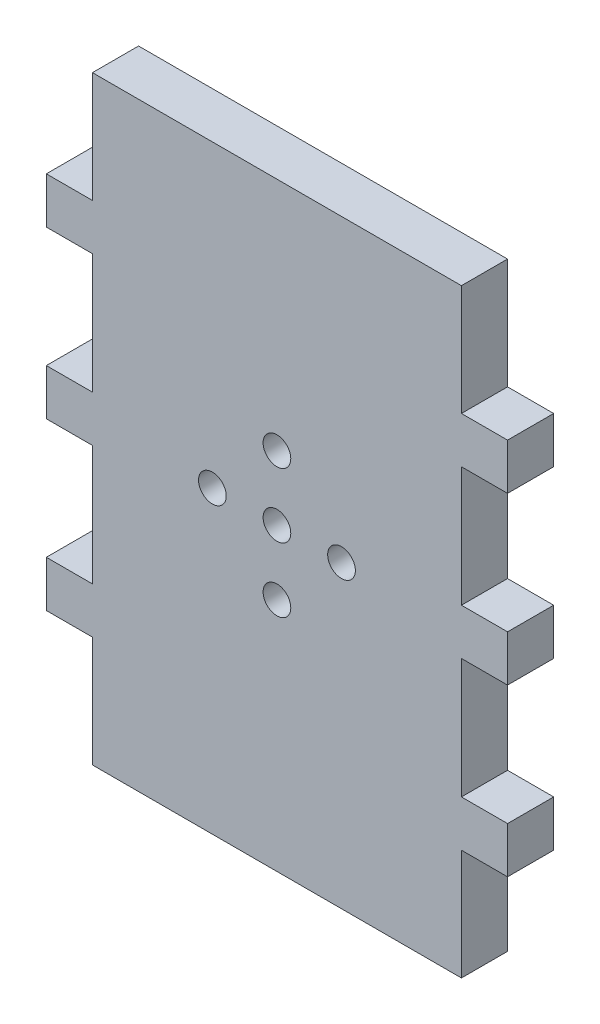
SolidWorks part; units mm, degrees
ref_plane "前视基准面" through (0, 0, 0) normal (0, 0, 1) x (1, 0, 0)
ref_plane "上视基准面" through (0, 0, 0) normal (0, 1, 0) x (1, 0, 0)
ref_plane "右视基准面" through (0, 0, 0) normal (1, 0, 0) x (0, 0, -1)
other "Configuration Table"
sketch "草图3" plane through (0, 0, 0) normal (0, 0, 1) x (1, 0, 0)
  line L0 (0, 0) -> (0, -12)
  line L1 (0, 0) -> (40, 0)
  line L3 (0, -65) -> (40, -65)
  line L4 (40, 0) -> (40, -12)
  line L5 (-5, -12) -> (-5, -17)
  line L6 (20, 0) -> (20, -65) construction
  line L7 (40, -12) -> (45, -12)
  line L8 (45, -12) -> (45, -17)
  line L9 (45, -17) -> (40, -17)
  line L10 (40, -17) -> (40, -30)
  line L11 (40, -30) -> (45, -30)
  line L12 (45, -30) -> (45, -35)
  line L13 (45, -35) -> (40, -35)
  line L14 (40, -65) -> (40, -53)
  line L15 (40, -53) -> (45, -53)
  line L16 (45, -53) -> (45, -48)
  line L17 (45, -48) -> (40, -48)
  line L18 (-5, -48) -> (0, -48)
  line L19 (-5, -53) -> (-5, -48)
  line L20 (0, -53) -> (-5, -53)
  line L21 (-5, -35) -> (0, -35)
  line L22 (-5, -30) -> (-5, -35)
  line L23 (0, -30) -> (-5, -30)
  line L24 (-5, -17) -> (0, -17)
  line L26 (0, -12) -> (-5, -12)
  line L27 (0, -17) -> (0, -30)
  line L28 (0, -35) -> (0, -48)
  line L29 (0, -53) -> (0, -65)
  line L31 (40, -35) -> (40, -48)
  circle A0 centre (20, -32.5) radius 1.5
  circle A2 centre (27, -32.5) radius 1.5
  circle A3 centre (20, -25.5) radius 1.5
  circle A4 centre (13, -32.5) radius 1.5
  circle A5 centre (20, -39.5) radius 1.5
  dimension "D6" = 3
  dimension "D12" = 3
  dimension "D13" = 3
  dimension "D14" = 3
  dimension "D1" = 65
  dimension "D2" = 40
  dimension "D3" = 12
  dimension "D4" = 5
  dimension "D5" = 5
  dimension "D7" = 5
  dimension "D8" = 5
  dimension "D9" = 12
  dimension "D10" = 5
  dimension "D11" = 5
extrude "凸台-拉伸2" add sketch "草图3" along normal blind 5
